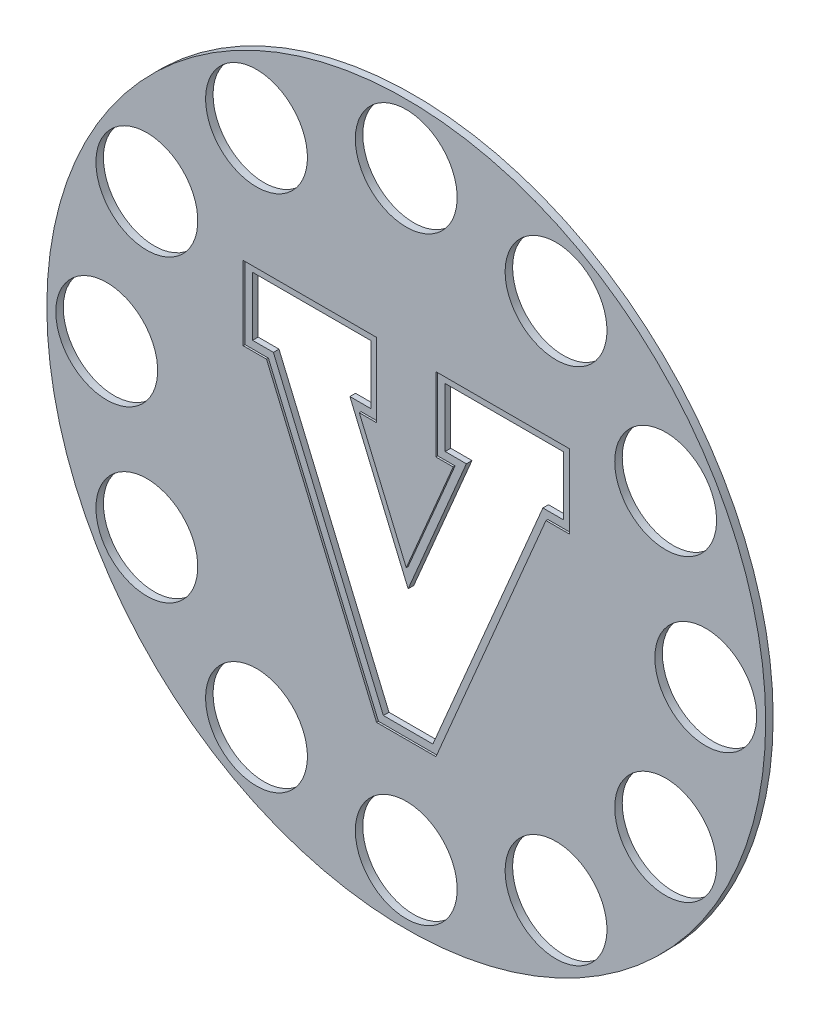
SolidWorks part; units mm, degrees
material "Mahogany"
ref_plane "Front Plane" through (0, 0, 0) normal (0, 0, 1) x (1, 0, 0)
ref_plane "Top Plane" through (0, 0, 0) normal (0, 1, 0) x (1, 0, 0)
ref_plane "Right Plane" through (0, 0, 0) normal (1, 0, 0) x (0, 0, -1)
sketch "Sketch1" plane through (0, 0, 0) normal (0, 0, 1) x (1, 0, 0)
  line L0 (0, 508) -> (0, 0) construction
  line L1 (-9.0217, 784.0457) -> (1590.9783, 784.0457) construction
  line L2 (-263.8171, 221.7679) -> (-62.7583, 221.7679)
  line L3 (-62.7583, 221.7679) -> (-62.7583, 121.8195)
  line L4 (-62.7583, 121.8195) -> (-98.7862, 121.8195)
  line L5 (-98.7862, 121.8195) -> (0, -111.1996)
  line L7 (41.9693, -318.2865) -> (-41.9693, -318.2865)
  line L8 (-41.9693, -318.2865) -> (-228.5479, 121.8195)
  line L9 (-228.5479, 121.8195) -> (-263.8171, 121.8195)
  line L10 (-263.8171, 121.8195) -> (-263.8171, 221.7679)
  line L11 (228.5479, 121.8195) -> (263.8171, 121.8195)
  line L12 (41.9693, -318.2865) -> (228.5479, 121.8195)
  line L13 (98.7862, 121.8195) -> (0, -111.1996)
  line L14 (62.7583, 121.8195) -> (98.7862, 121.8195)
  line L15 (62.7583, 221.7679) -> (62.7583, 121.8195)
  line L16 (263.8171, 221.7679) -> (62.7583, 221.7679)
  line L17 (263.8171, 121.8195) -> (263.8171, 221.7679)
  circle A0 centre (0, 0) radius 609.6
  circle A2 centre (0, 508) radius 86.36
  circle A3 centre (254, 439.9409) radius 86.36
  circle A4 centre (439.9409, 254) radius 86.36
  circle A5 centre (508, 0) radius 86.36
  circle A6 centre (439.9409, -254) radius 86.36
  circle A7 centre (254, -439.9409) radius 86.36
  circle A8 centre (0, -508) radius 86.36
  circle A9 centre (-254, -439.9409) radius 86.36
  circle A10 centre (-439.9409, -254) radius 86.36
  circle A11 centre (-508, 0) radius 86.36
  circle A12 centre (-439.9409, 254) radius 86.36
  circle A13 centre (-254, 439.9409) radius 86.36
  point P29 (0, 0)
  dimension "D1" = 1219.2
  dimension "D2" = 172.72
  dimension "D3" = 508
  dimension "D4" = 12
extrude "Boss-Extrude1" add sketch "Sketch1" along normal blind 12.7
sketch "Sketch2" plane through (0, 0, 12.7) normal (0, 0, 1) x (1, 0, 0)
  line L126 (11.6927, -106.2426) -> (-79.608, 109.1195)
  line L127 (-236.958, 109.1195) -> (-53.6619, -323.2435)
  line L128 (-276.5171, 109.1195) -> (-236.958, 109.1195)
  line L129 (-79.608, 109.1195) -> (-50.0583, 109.1195)
  line L130 (-50.0583, 109.1195) -> (-50.0583, 234.4679)
  line L131 (-276.5171, 234.4679) -> (-276.5171, 109.1195)
  line L132 (-50.0583, 234.4679) -> (-276.5171, 234.4679)
  line L133 (0, -78.6617) -> (-79.608, 109.1195)
  line L135 (-276.5171, 109.1195) -> (-236.958, 109.1195)
  line L136 (-79.608, 109.1195) -> (-50.0583, 109.1195)
  line L137 (-50.0583, 109.1195) -> (-50.0583, 234.4679)
  line L138 (-276.5171, 234.4679) -> (-276.5171, 109.1195)
  line L139 (-50.0583, 234.4679) -> (-276.5171, 234.4679)
  line L198 (0, -78.6617) -> (-87.0935, 126.7765)
  line L199 (-240.2406, 116.8625) -> (-50.3794, -330.9865)
  line L200 (-50.3794, -330.9865) -> (50.3794, -330.9865)
  line L201 (50.3794, -330.9865) -> (236.958, 109.1195)
  line L202 (236.958, 109.1195) -> (276.5171, 109.1195)
  line L203 (276.5171, 109.1195) -> (276.5171, 234.4679)
  line L204 (276.5171, 234.4679) -> (50.0583, 234.4679)
  line L205 (50.0583, 234.4679) -> (50.0583, 109.1195)
  line L206 (50.0583, 109.1195) -> (79.608, 109.1195)
  line L207 (79.608, 109.1195) -> (0, -78.6617)
  line L208 (0, -78.6617) -> (-79.608, 109.1195)
  line L209 (-236.958, 109.1195) -> (-50.3794, -330.9865)
  line L210 (-50.3794, -330.9865) -> (50.3794, -330.9865)
  line L211 (50.3794, -330.9865) -> (236.958, 109.1195)
  line L212 (236.958, 109.1195) -> (276.5171, 109.1195)
  line L213 (276.5171, 109.1195) -> (276.5171, 234.4679)
  line L214 (276.5171, 234.4679) -> (50.0583, 234.4679)
  line L215 (50.0583, 234.4679) -> (50.0583, 109.1195)
  line L216 (50.0583, 109.1195) -> (79.608, 109.1195)
  line L217 (79.608, 109.1195) -> (0, -78.6617)
  line M14 (-228.5479, 121.8195) -> (-263.8171, 121.8195)
  line M15 (-263.8171, 121.8195) -> (-263.8171, 221.7679)
  line M16 (-263.8171, 221.7679) -> (-62.7583, 221.7679)
  line M17 (-62.7583, 221.7679) -> (-62.7583, 121.8195)
  line M18 (-62.7583, 121.8195) -> (-98.7862, 121.8195)
  line M19 (-98.7862, 121.8195) -> (0, -111.1996)
  line M20 (0, -111.1996) -> (98.7862, 121.8195)
  line M21 (98.7862, 121.8195) -> (62.7583, 121.8195)
  line M22 (62.7583, 121.8195) -> (62.7583, 221.7679)
  line M23 (62.7583, 221.7679) -> (263.8171, 221.7679)
  line M24 (263.8171, 221.7679) -> (263.8171, 121.8195)
  line M25 (263.8171, 121.8195) -> (228.5479, 121.8195)
  line M26 (228.5479, 121.8195) -> (41.9693, -318.2865)
  line M27 (41.9693, -318.2865) -> (-41.9693, -318.2865)
  line M28 (-41.9693, -318.2865) -> (-228.5479, 121.8195)
  dimension "D1" = 12.7
  dimension "D2" = 12.7
extrude "Cut-Extrude1" cut sketch "Sketch2" against normal blind 3.175 and the other way through all contours L216 L217 L133 L136 L137 L139 L138 L135 L209 L210 L211 L212 L213 L214 L215 M28 M14 M15 M16 M17 M18 M19 M20 M21 M22 M23 M24 M25 M26 M27 region at (-44.2826, 9.3282, 12.7) region at (47.086, 12.1418, 12.7)
sketch "Sketch3" plane through (0, 0, 12.7) normal (0, 0, 1) x (1, 0, 0)
  line B0 (50.0583, 109.1195) -> (79.608, 109.1195)
  line B1 (79.608, 109.1195) -> (0, -78.6617)
  line B2 (0, -78.6617) -> (-79.608, 109.1195)
  line B3 (-79.608, 109.1195) -> (-50.0583, 109.1195)
  line B4 (-50.0583, 109.1195) -> (-50.0583, 234.4679)
  line B5 (-50.0583, 234.4679) -> (-276.5171, 234.4679)
  line B6 (-276.5171, 234.4679) -> (-276.5171, 109.1195)
  line B7 (-276.5171, 109.1195) -> (-236.958, 109.1195)
  line B8 (-236.958, 109.1195) -> (-50.3794, -330.9865)
  line B9 (-50.3794, -330.9865) -> (50.3794, -330.9865)
  line B10 (50.3794, -330.9865) -> (236.958, 109.1195)
  line B11 (236.958, 109.1195) -> (276.5171, 109.1195)
  line B12 (276.5171, 109.1195) -> (276.5171, 234.4679)
  line B13 (276.5171, 234.4679) -> (50.0583, 234.4679)
  line B14 (50.0583, 234.4679) -> (50.0583, 109.1195)
  line B15 (41.9693, -318.2865) -> (-41.9693, -318.2865)
  line B16 (228.5479, 121.8195) -> (41.9693, -318.2865)
  line B17 (263.8171, 121.8195) -> (228.5479, 121.8195)
  line B18 (263.8171, 221.7679) -> (263.8171, 121.8195)
  line B19 (62.7583, 221.7679) -> (263.8171, 221.7679)
  line B20 (62.7583, 121.8195) -> (62.7583, 221.7679)
  line B21 (98.7862, 121.8195) -> (62.7583, 121.8195)
  line B22 (0, -111.1996) -> (98.7862, 121.8195)
  line B23 (-98.7862, 121.8195) -> (0, -111.1996)
  line B24 (-62.7583, 121.8195) -> (-98.7862, 121.8195)
  line B25 (-62.7583, 221.7679) -> (-62.7583, 121.8195)
  line B26 (-263.8171, 221.7679) -> (-62.7583, 221.7679)
  line B27 (-263.8171, 121.8195) -> (-263.8171, 221.7679)
  line B28 (-228.5479, 121.8195) -> (-263.8171, 121.8195)
  line B29 (-41.9693, -318.2865) -> (-228.5479, 121.8195)
sketch_block_instance "Block1-1"
sketch_block "Block1"
